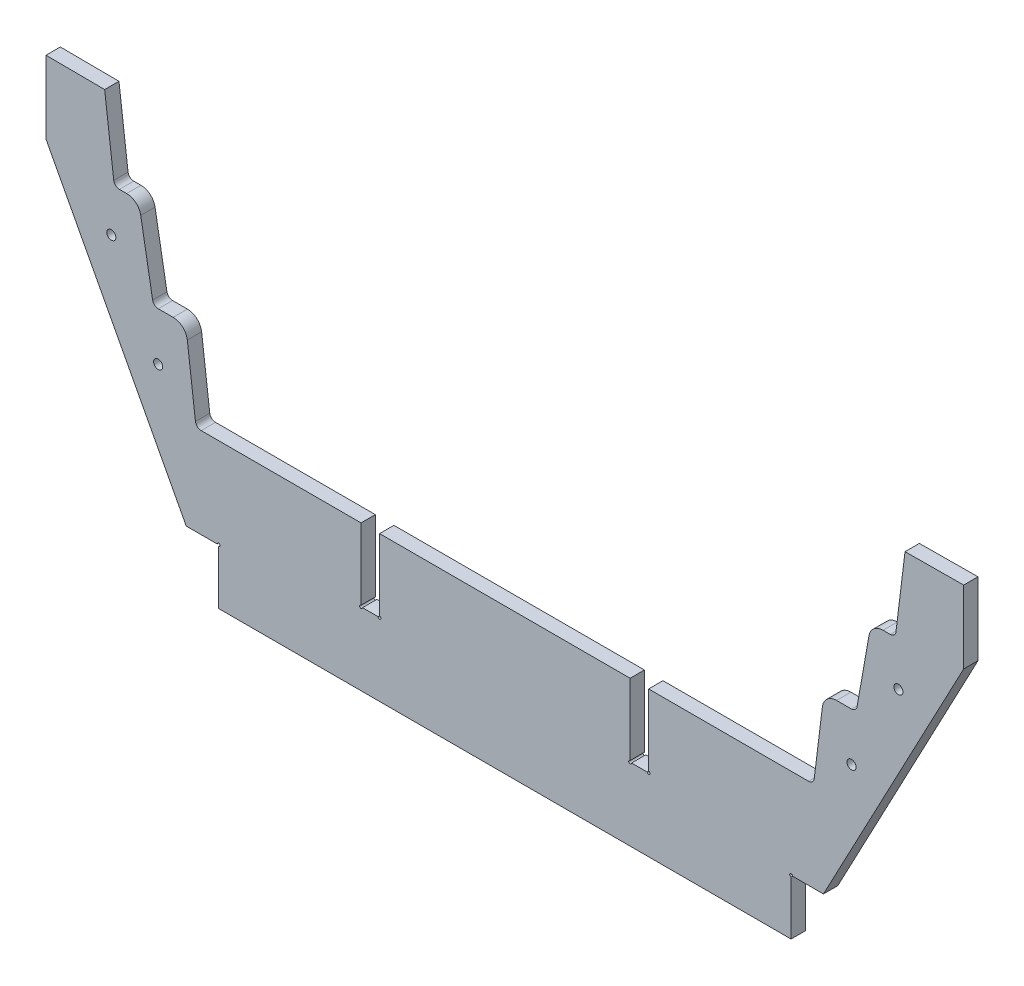
SolidWorks part; units mm, degrees
material "PC High Viscosity"
ref_plane "Front Plane" through (0, 0, 0) normal (0, 0, 1) x (1, 0, 0)
ref_plane "Top Plane" through (0, 0, 0) normal (0, 1, 0) x (1, 0, 0)
ref_plane "Right Plane" through (0, 0, 0) normal (1, 0, 0) x (0, 0, -1)
ref_axis "Axis1" through (0, -55, 0) along (0, 1, 0)
sketch "Sketch2" plane through (0, 0, 0) normal (0, 0, 1) x (1, 0, 0)
  line L0 (243.1008, -174.022) -> (243.1008, -172.622) construction
  line L1 (273.7035, -115.348) -> (273.7035, -113.948) construction
  line L3 (280.6135, -64.0443) -> (274.8035, -111.3631) construction
  line L5 (254, -117.348) -> (244.8482, -169.2507) construction
  line L7 (220.98, -176.022) -> (213.7689, -234.7515) construction
  line L10 (320.6135, -114.8443) -> (222.623, -300)
  line L11 (241.1008, -176.022) -> (220.98, -176.022) construction
  line L14 (254, -117.348) -> (271.7035, -117.348) construction
  line L16 (282.832, -64.3167) -> (276.4774, -116.0707) construction
  line L18 (255.8756, -119.5832) -> (269.3084, -119.5832)
  line L20 (0, -338.582) -> (-41.5838, -338.582) construction
  line L21 (-94, -197.2355) -> (-94, -248.5012) construction
  line L22 (87.523, -236.982) -> (0, -236.982)
  line L24 (212.2081, -236.982) -> (100.477, -236.982)
  line L25 (0, -447.6144) -> (0, 0) construction
  line L26 (100.477, -236.982) -> (100.477, -286.782)
  line L27 (99.477, -287.782) -> (88.523, -287.782)
  line L28 (87.523, -236.982) -> (87.523, -286.782)
  line L29 (255.8756, -119.5832) -> (246.1126, -174.9518)
  line L30 (0, -236.982) -> (0, -338.582)
  line L31 (99.477, -287.782) -> (88.523, -287.782) construction
  line L32 (100.477, -287.782) -> (87.523, -287.782) construction
  line L33 (212.9309, -236.3443) -> (240.0746, -267.0247) construction
  line L34 (241.1008, -178.2572) -> (222.9575, -178.2572) construction
  line L35 (274.8126, -118.2238) -> (276.0893, -119.2319) construction
  line L36 (320.6135, -64.0443) -> (320.6135, -114.8443)
  line L45 (200, -338.582) -> (0, -338.582)
  line L46 (222.623, -300) -> (201, -300)
  line L48 (200, -338.582) -> (200, -301)
  line L51 (275, -150) -> (242.2565, -211.8697) construction
  line L52 (275, -150) -> (248.2426, -150) construction
  line L54 (242.1733, -178.2572) -> (222.9575, -178.2572)
  line L55 (222.9575, -178.2572) -> (216.1783, -233.4695)
  line L56 (320.6135, -64.0443) -> (279.6303, -64.3398)
  line L57 (255.5136, -186.8201) -> (274.0073, -202.908) construction
  line L58 (255.8756, -119.5832) -> (271.7035, -119.5832) construction
  line L59 (282.832, -64.3167) -> (277.022, -111.6355) construction
  line L60 (255.8756, -119.5832) -> (247.0494, -169.6388) construction
  line L61 (275.9387, -115.348) -> (275.9387, -114.6622) construction
  line L62 (245.336, -174.022) -> (245.336, -173.4639) construction
  line L63 (222.9575, -178.2572) -> (215.9875, -235.024) construction
  line L64 (279.6303, -64.3398) -> (273.2786, -116.0707)
  line L65 (279.6807, -63.9298) -> (273.3261, -115.6837) construction
  arc A0 (271.7035, -117.348) -> (273.7035, -115.348) centre (271.7035, -115.348) ccw construction
  arc A3 (243.1008, -172.622) -> (244.8482, -169.2507) centre (238.5946, -168.148) ccw construction
  arc A4 (241.1008, -176.022) -> (243.1008, -174.022) centre (241.1008, -174.022) ccw construction
  arc A7 (273.7035, -113.948) -> (274.8035, -111.3631) centre (269.7613, -110.744) ccw construction
  arc A8 (99.477, -287.782) -> (100.477, -286.782) centre (100.477, -287.782) ccw
  arc A9 (87.523, -286.782) -> (88.523, -287.782) centre (87.523, -287.782) ccw
  arc A15 (201, -300) -> (200, -301) centre (200, -300) ccw
  circle A16 centre (275, -150) radius 3.175
  circle A17 centre (242.2565, -211.8697) radius 3.175
  arc A22 (241.1008, -178.2572) -> (245.336, -174.022) centre (241.1008, -174.022) ccw construction
  arc A23 (245.336, -173.4639) -> (247.0494, -169.6388) centre (238.5946, -168.148) ccw construction
  arc A24 (275.9387, -114.6622) -> (277.022, -111.6355) centre (269.7613, -110.744) ccw construction
  arc A25 (271.7035, -119.5832) -> (275.9387, -115.348) centre (271.7035, -115.348) ccw construction
  arc A26 (276.4774, -116.0707) -> (272.8491, -119.5686) centre (272.5072, -115.5832) cw construction
  arc A27 (246.1126, -174.9518) -> (242.1733, -178.2572) centre (242.1733, -174.2572) cw
  arc A28 (212.2081, -236.982) -> (216.1783, -233.4695) centre (212.2081, -232.982) ccw
  arc A29 (273.2786, -116.0707) -> (269.3084, -119.5832) centre (269.3084, -115.5832) cw
  point P45 (94, -287.782)
  dimension "D12" = 1
  dimension "D15" = 2
  dimension "D19" = 70
  dimension "D18" = 4
  dimension "D16" = 50.8
  dimension "D22" = 6.35
  dimension "D23" = 4
  dimension "D26" = 4
  dimension "D3" = 64.0443
  dimension "D4" = 101.6
  dimension "D5" = 94
  dimension "D6" = 50.8
  dimension "D7" = 94
  dimension "D8" = 12.954
  dimension "D9" = 200
  dimension "D10" = 40
  dimension "D11" = 2.2352
  dimension "D13" = 12.954
  dimension "D14" = 222.623
  dimension "D17" = 300
  dimension "D20" = 275
  dimension "D21" = 150
  dimension "D24" = 37.582
  dimension "D25" = 185.1557
extrude "Boss-Extrude1" add sketch "Sketch2" along normal blind 10 contours L3 A7 L1 L14 L5 A3 L0 L11 L7 L24 L26 A8 L27 A9 L28 L22 L30 region at (157.7052, -248.7453, 0)
fillet "Fillet1" radius 10 2 edges at (222.9575, -178.2572, 5) (255.8756, -119.5832, 5)
mirror "Mirror1" about plane through (0, 0, 10) normal (1, 0, 0) of "Fillet1", "Boss-Extrude1"
